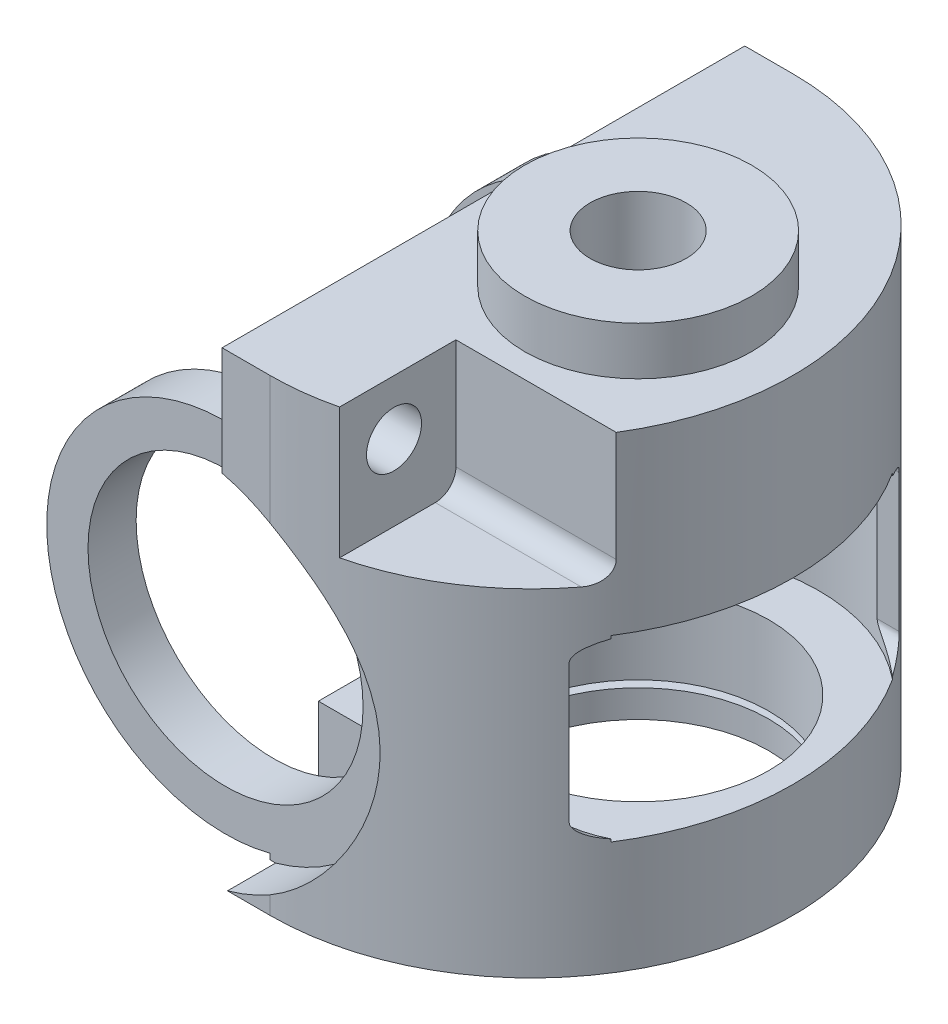
SolidWorks part; units mm, degrees
ref_plane "Plan de face" through (0, 0, 0) normal (0, 0, 1) x (1, 0, 0)
ref_plane "Plan de dessus" through (0, 0, 0) normal (0, 1, 0) x (1, 0, 0)
ref_plane "Plan de droite" through (0, 0, 0) normal (1, 0, 0) x (0, 0, -1)
sketch "Sketch2" plane through (0, 0, 0) normal (0, 1, 0) x (1, 0, 0)
  line L0 (-3.5, -19) -> (-3.5, 19)
  line L1 (-3.5, 19) -> (0, 19)
  line L2 (-3.5, -19) -> (0, -19)
  line L3 (19, 0) -> (19, 16.5672) construction
  arc A0 (0, -19) -> (0, 19) centre (0, 0) ccw
  circle A1 centre (7.75, 0) radius 3.5
  point P7 (-3.5, 0)
  dimension "D1" = 19
  dimension "D3" = 22.5
  dimension "D4" = 11.25
  dimension "D5" = 7
  dimension "D2" = 38
extrude "Boss-Extrude1" add sketch "Sketch2" along normal blind 34
sketch "Sketch19" plane through (0, 34, 0) normal (0, 1, 0) x (1, 0, 0)
  circle A0 centre (7.75, 0) radius 8.25
  circle A1 centre (7.75, 0) radius 3.5
  dimension "D1" = 16.5
  dimension "D2" = 7
extrude "Boss-Extrude3" add sketch "Sketch19" along normal blind 3.5
sketch "Sketch7" plane through (0, 0, 19) normal (0, 0, -1) x (-1, 0, 0)
  line L0 (6.75, 13) -> (0, 0) construction
  circle A3 centre (6.75, 13) radius 13.5
  dimension "D1" = 13
  dimension "D2" = 6.75
  dimension "D3" = 27
extrude "Cut-Extrude4" cut sketch "Sketch7" along normal blind 3.5 contours A3
sketch "Sketch25" plane through (0, 0, 15.5) normal (0, 0, 1) x (1, 0, 0)
  circle A0 centre (-6.75, 13) radius 13
  dimension "D1" = 26
extrude "Boss-Extrude4" add sketch "Sketch25" against normal blind 3.5
sketch "Sketch27" plane through (0, 0, 15.5) normal (0, 0, 1) x (1, 0, 0)
  circle A0 centre (-6.75, 13) radius 10
  dimension "D1" = 20
extrude "Cut-Extrude13" cut sketch "Sketch27" against normal up to surface (3.5 mm away) up to face at (-11.625, 13, 12)
pattern_linear "LPattern3" count 2 spacing 34.5 along (0, 0, -1) of "Cut-Extrude4"
pattern_linear "LPattern4" count 2 spacing 27.5 along (0, 0, -1) of "Boss-Extrude4", "Cut-Extrude13"
sketch "Sketch6" plane through (-3.5, 0, 0) normal (1, 0, 0) x (0, 0, -1)
  line L0 (15.5, 0) -> (-15.5, 0) construction
  line L1 (12, 21.25) -> (-12, 21.25)
  line L2 (12, 21.25) -> (12, 8.25)
  line L3 (12, 8.25) -> (-12, 8.25)
  line L4 (-12, 21.25) -> (-12, 8.25)
  point P1 (0, 8.25)
  dimension "D1" = 8.25
  dimension "D2" = 13
  dimension "D3" = 24
extrude "Cut-Extrude3" cut sketch "Sketch6" along normal through all
fillet "Fillet2" radius 3.5 2 edges at (8.3904, 8.25, -12) (6.8161, 21.25, -12) second distance 1.5 first distance on face at (7.75, 8.25, 3.5) first distance on face at (7.75, 21.25, -3.5)
fillet "Fillet3" radius 3.5 2 edges at (8.3904, 8.25, 12) (6.8161, 21.25, 12) second distance 1.5 first distance on face at (7.75, 8.25, 3.5) first distance on face at (7.75, 21.25, -3.5)
sketch "Sketch16" plane through (-3.5, 0, 0) normal (-1, 0, 0) x (0, 0, 1)
  line L1 (-19, 34) -> (19, 34) construction
  line L2 (-19, 34) -> (-19, 26.103) construction
  point P0 (-11, 31.5)
  dimension "D1" = 8
  dimension "D2" = 2.5
hole_wizard "M2 Tapped Hole1" positions "Sketch16" profile "Sketch15" tap size "M2" standard "ISO"
sketch "Sketch15" plane through (-3.5, 31.5, -11) normal (0, 1, 0) x (0, 0, 1)
  line L0 (0, 0) -> (0, 5.9807)
  line L1 (0, 5.9807) -> (0.8, 5.5)
  line L2 (0.8, 5.5) -> (0.8, 0)
  line L5 (0.8, 0) -> (0, 0)
  line L10 (0, 5.9807) -> (-0.8, 5.5) construction
  line L11 (0, -6.35) -> (0, 107.95) construction
  dimension "Tap Drill Dia." = 1.6
  dimension "Tap Drill Depth" = 5.5
  dimension "Drill Angle" = 118
cosmetic thread "Hole Thread1" parameters "D1"=4.5, "D2"=2
sketch "Sketch17" plane through (-3.5, 0, 0) normal (-1, 0, 0) x (0, 0, 1)
  line L1 (-19, 34) -> (19, 34) construction
  line L2 (19, 34) -> (19, 26.103) construction
  circle A1 centre (14.5, 30) radius 2
  dimension "D1" = 4
  dimension "D2" = 4.5
  dimension "D3" = 4
extrude "Cut-Extrude5" cut sketch "Sketch17" against normal blind 8
sketch "Sketch18" plane through (4.5, 0, 0) normal (-1, 0, 0) x (0, 0, 1)
  line L0 (10, 34) -> (14.5, 30) construction
  line L6 (0, 0) -> (0, 34) construction
  line L7 (-15.5, 0) -> (15.5, 0) construction
  line L8 (10, 26) -> (10, 34)
  line L9 (19, 34) -> (10, 34)
  line L10 (19, 24.5) -> (19, 34)
  line L11 (19, 24.5) -> (11.5, 24.5)
  arc A3 (10, 26) -> (11.5, 24.5) centre (11.5, 26) ccw
  dimension "D1" = 9
  dimension "D2" = 9.5
  dimension "D3" = 1.5
  dimension "D4" = 4
  dimension "D5" = 8
  dimension "D6" = 7.5
  dimension "D7" = 4.5
extrude "Cut-Extrude6" cut sketch "Sketch18" against normal up to next
sketch "Sketch20" plane through (0, 21.25, 0) normal (0, -1, 0) x (1, 0, 0)
  circle A0 centre (7.75, 0) radius 9.75
  dimension "D1" = 19.5
extrude "Cut-Extrude7" cut sketch "Sketch20" against normal blind 6.25
sketch "Sketch21" plane through (0, 27.5, 0) normal (0, -1, 0) x (1, 0, 0)
  circle A0 centre (7.75, 0) radius 8.5
  dimension "D1" = 17
extrude "Cut-Extrude8" cut sketch "Sketch21" against normal blind 0.5
sketch "Sketch22" plane through (0, 8.25, 0) normal (0, 1, 0) x (1, 0, 0)
  circle A0 centre (7.75, 0) radius 9.5
  dimension "D1" = 19
extrude "Cut-Extrude9" cut sketch "Sketch22" against normal blind 5.75 and the other way blind 1
sketch "Sketch23" plane through (0, 2.5, 0) normal (0, 1, 0) x (1, 0, 0)
  circle A0 centre (7.75, 0) radius 10.5
  dimension "D1" = 21
extrude "Cut-Extrude10" cut sketch "Sketch23" against normal blind 0.5
sketch "Sketch24" plane through (0, 2, 0) normal (0, 1, 0) x (1, 0, 0)
  circle A0 centre (7.75, 0) radius 9.5
  dimension "D1" = 19
extrude "Cut-Extrude11" cut sketch "Sketch24" against normal blind 2
sketch "Sketch30" plane through (0, 8.25, 0) normal (0, 1, 0) x (1, 0, 0)
  circle A0 centre (7.75, 0) radius 13.15
  dimension "D1" = 26.3
extrude "Cut-Extrude14" cut sketch "Sketch30" along normal blind 13
